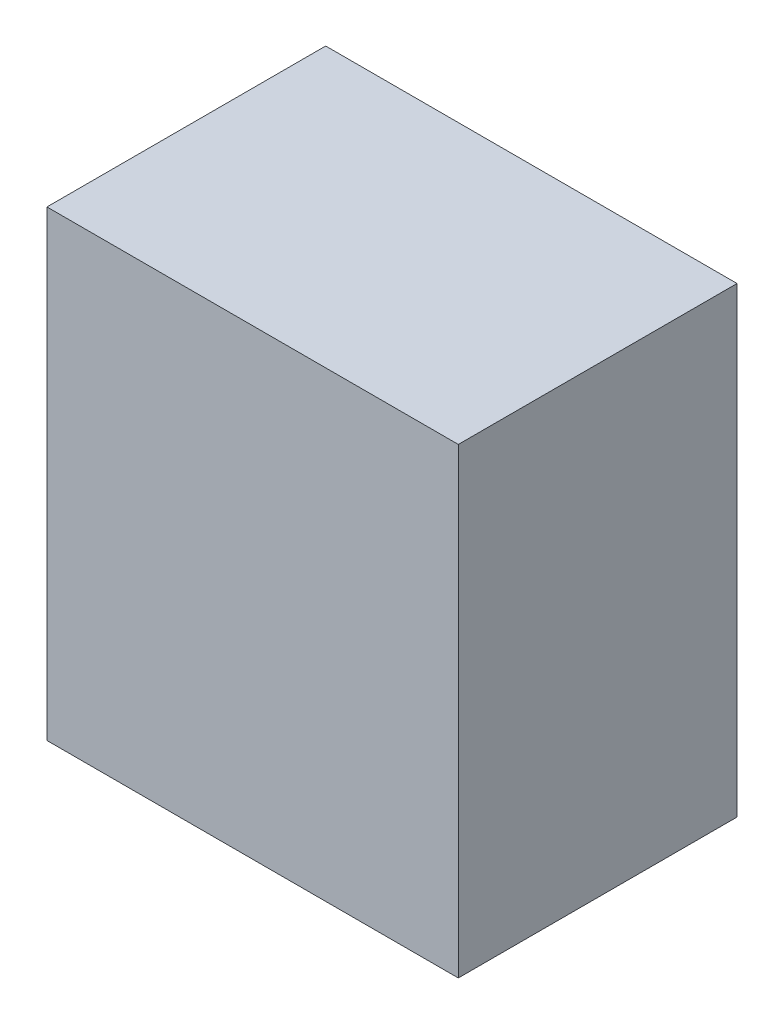
SolidWorks part; units mm, degrees
ref_plane "前视基准面" through (0, 0, 0) normal (0, 0, 1) x (1, 0, 0)
ref_plane "上视基准面" through (0, 0, 0) normal (0, 1, 0) x (1, 0, 0)
ref_plane "右视基准面" through (0, 0, 0) normal (1, 0, 0) x (0, 0, -1)
sketch "草图1" plane through (0, 0, 0) normal (0, 0, 1) x (1, 0, 0)
  line L0 (-3.04, 0) -> (3.04, 0) construction
  line L1 (-3.04, 3.415) -> (3.04, 3.415)
  line L2 (-3.04, 3.415) -> (-3.04, -3.415)
  line L3 (-3.04, -3.415) -> (3.04, -3.415)
  line L4 (3.04, 3.415) -> (3.04, -3.415)
  dimension "D1" = 6.08
  dimension "D2" = 6.83
extrude "拉伸1" add sketch "草图1" along normal blind 4.12
sketch "草图2" plane through (0, 0, 0) normal (0, 0, -1) x (-1, 0, 0)
  line L0 (-3.04, 3.415) -> (3.04, 3.415) construction
  line L1 (0, 0) -> (0, 0.565) construction
  circle A0 centre (0, 0.565) radius 2.35
  dimension "D1" = 4.7
  dimension "D2" = 2.85
extrude "拉伸2" add sketch "草图2" along normal blind 0.1
dome "圆顶1" faces to dome 1 distance 1.45 reverse direction no elliptical dome no face at (-2.35, 0.565, -0.1) parameters "D1"=1.45
sketch "草图3" plane through (3.04, 0, 0) normal (1, 0, 0) x (0, 0, -1)
  line L0 (1.55, 0.565) -> (1.55, -2.9803)
  line L1 (-4.12, -3.415) -> (-4.12, 3.415) construction
  arc A0 (0.1, -1.785) -> (0.1, 2.915) centre (-1.0793, 0.565) ccw construction
  arc A1 (0.1, -1.785) -> (0.1, 2.915) centre (-1.0793, 0.565) ccw
  dimension "D1" = 5.67
